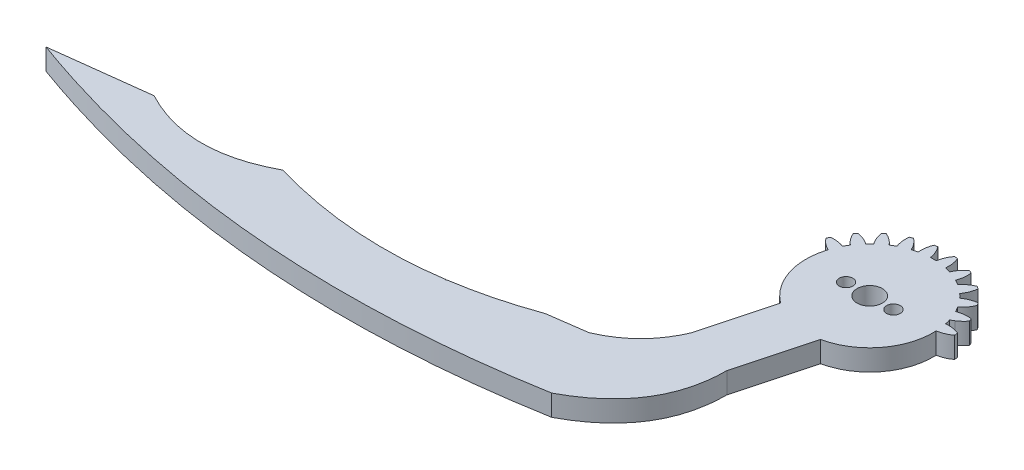
SolidWorks part; units mm, degrees
note: The reader was unsure of these and kept them because the rebuilt part matched: shared geometry of "Sketch6<3>".
ref_plane "Front Plane" through (0, 0, 0) normal (0, 0, 1) x (1, 0, 0)
ref_plane "Top Plane" through (0, 0, 0) normal (0, 1, 0) x (1, 0, 0)
ref_plane "Right Plane" through (0, 0, 0) normal (1, 0, 0) x (0, 0, -1)
sketch "Sketch1" plane through (0, 0, 0) normal (0, 1, 0) x (1, 0, 0)
  line L0 (20.6437, 4) -> (2.0816, 4)
  line L1 (2.0816, -4) -> (20.6437, -4)
  arc A0 (2.0816, 4) -> (3.5217, 5.3071) centre (-0.7683, 8.5867) ccw
  arc A1 (3.5217, 5.3071) -> (3.2829, 5.8838) centre (-10.1063, 0) ccw
  arc A2 (3.2829, 5.8838) -> (0.6271, 5.5703) centre (2.5684, 0.5313) ccw
  arc A3 (0.6271, 5.5703) -> (0.0844, 6.5103) centre (-10.1063, 0) ccw
  arc A4 (0.0844, 6.5103) -> (1.6838, 8.6535) centre (-3.3089, 10.711) ccw
  arc A5 (1.6838, 8.6535) -> (1.3038, 9.1487) centre (-10.1063, 0) ccw
  arc A6 (1.3038, 9.1487) -> (-1.1803, 8.1585) centre (1.999, 3.7936) ccw
  arc A7 (-1.1803, 8.1585) -> (-1.9479, 8.926) centre (-10.1063, 0) ccw
  arc A8 (-1.9479, 8.926) -> (-0.9576, 11.4102) centre (-6.3127, 12.1053) ccw
  arc A9 (-0.9576, 11.4102) -> (-1.4528, 11.7901) centre (-10.1063, 0) ccw
  arc A10 (-1.4528, 11.7901) -> (-3.596, 10.1907) centre (0.6046, 6.7975) ccw
  arc A11 (-3.596, 10.1907) -> (-4.5361, 10.7334) centre (-10.1063, 0) ccw
  arc A12 (-4.5361, 10.7334) -> (-4.2225, 13.3892) centre (-9.5751, 12.6747) ccw
  arc A13 (-4.2225, 13.3892) -> (-4.7992, 13.6281) centre (-10.1063, 0) ccw
  arc A14 (-4.7992, 13.6281) -> (-6.4554, 11.5285) centre (-1.5196, 9.3381) ccw
  arc A15 (-6.4554, 11.5285) -> (-7.5039, 11.8094) centre (-10.1063, 0) ccw
  arc A16 (-7.5039, 11.8094) -> (-7.8884, 14.4558) centre (-12.8736, 12.3803) ccw
  arc A17 (-7.8884, 14.4558) -> (-8.5072, 14.5373) centre (-10.1063, 0) ccw
  arc A18 (-8.5072, 14.5373) -> (-9.5636, 12.0806) centre (-4.2291, 11.2423) ccw
  arc A19 (-9.5636, 12.0806) -> (-10.6491, 12.0806) centre (-10.1063, 0) ccw
  arc A20 (-10.6491, 12.0806) -> (-11.7054, 14.5373) centre (-15.9836, 11.2423) ccw
  arc A21 (-11.7054, 14.5373) -> (-12.3243, 14.4558) centre (-10.1063, 0) ccw
  arc A22 (-12.3243, 14.4558) -> (-12.7088, 11.8094) centre (-7.3391, 12.3803) ccw
  arc A23 (-12.7088, 11.8094) -> (-13.7573, 11.5285) centre (-10.1063, 0) ccw
  arc A24 (-13.7573, 11.5285) -> (-15.4135, 13.6281) centre (-18.6931, 9.3381) ccw
  arc A25 (-15.4135, 13.6281) -> (-15.9901, 13.3892) centre (-10.1063, 0) ccw
  arc A26 (-15.9901, 13.3892) -> (-15.6766, 10.7334) centre (-10.6376, 12.6747) ccw
  arc A27 (-15.6766, 10.7334) -> (-16.6166, 10.1907) centre (-10.1063, 0) ccw
  arc A28 (-16.6166, 10.1907) -> (-18.7599, 11.7901) centre (-20.8173, 6.7975) ccw
  arc A29 (-18.7599, 11.7901) -> (-19.255, 11.4102) centre (-10.1063, 0) ccw
  arc A30 (-19.255, 11.4102) -> (-18.2648, 8.926) centre (-13.9, 12.1053) ccw
  arc A31 (-18.2648, 8.926) -> (-19.0324, 8.1585) centre (-10.1063, 0) ccw
  arc A32 (-19.0324, 8.1585) -> (-21.5165, 9.1487) centre (-22.2117, 3.7936) ccw
  arc A33 (-21.5165, 9.1487) -> (-21.8965, 8.6535) centre (-10.1063, 0) ccw
  arc A34 (-21.8965, 8.6535) -> (-20.2971, 6.5103) centre (-16.9038, 10.711) ccw
  arc A35 (-20.2971, 6.5103) -> (-20.8398, 5.5703) centre (-10.1063, 0) ccw
  arc A36 (-20.8398, 5.5703) -> (-23.4956, 5.8838) centre (-22.7811, 0.5313) ccw
  arc A37 (-23.4956, 5.8838) -> (-23.7344, 5.3071) centre (-10.1063, 0) ccw
  arc A38 (-23.7344, 5.3071) -> (-21.6348, 3.6509) centre (-19.4444, 8.5867) ccw
  arc A39 (-21.6348, 3.6509) -> (-21.9157, 2.6025) centre (-10.1063, 0) ccw
  arc A40 (-21.9157, 2.6025) -> (-24.5622, 2.2179) centre (-22.4867, -2.7673) ccw
  arc A41 (-24.5622, 2.2179) -> (-24.6437, 1.5991) centre (-10.1063, 0) ccw
  arc A42 (-24.6437, 1.5991) -> (-22.1869, 0.5427) centre (-21.3486, 5.8773) ccw
  arc A43 (-22.1869, 0.5427) -> (-22.1869, -0.5427) centre (-10.1063, 0) ccw
  arc A44 (-22.1869, -0.5427) -> (-24.6437, -1.5991) centre (-21.3486, -5.8773) ccw
  arc A45 (-24.6437, -1.5991) -> (-24.5622, -2.2179) centre (-10.1063, 0) ccw
  arc A46 (-24.5622, -2.2179) -> (-21.9157, -2.6025) centre (-22.4867, 2.7673) ccw
  arc A47 (-21.9157, -2.6025) -> (-21.6348, -3.6509) centre (-10.1063, 0) ccw
  arc A48 (-21.6348, -3.6509) -> (-23.7344, -5.3071) centre (-19.4444, -8.5867) ccw
  arc A49 (-23.7344, -5.3071) -> (-23.4956, -5.8838) centre (-10.1063, 0) ccw
  arc A50 (-23.4956, -5.8838) -> (-20.8398, -5.5703) centre (-22.7811, -0.5313) ccw
  arc A51 (-20.8398, -5.5703) -> (-20.2971, -6.5103) centre (-10.1063, 0) ccw
  arc A52 (-20.2971, -6.5103) -> (-21.8965, -8.6535) centre (-16.9038, -10.711) ccw
  arc A53 (-21.8965, -8.6535) -> (-21.5165, -9.1487) centre (-10.1063, 0) ccw
  arc A54 (-21.5165, -9.1487) -> (-19.0324, -8.1585) centre (-22.2117, -3.7936) ccw
  arc A55 (-19.0324, -8.1585) -> (-18.2648, -8.926) centre (-10.1063, 0) ccw
  arc A56 (-18.2648, -8.926) -> (-19.255, -11.4102) centre (-13.9, -12.1053) ccw
  arc A57 (-19.255, -11.4102) -> (-18.7599, -11.7901) centre (-10.1063, 0) ccw
  arc A58 (-18.7599, -11.7901) -> (-16.6166, -10.1907) centre (-20.8173, -6.7975) ccw
  arc A59 (-16.6166, -10.1907) -> (-15.6766, -10.7334) centre (-10.1063, 0) ccw
  arc A60 (-15.6766, -10.7334) -> (-15.9901, -13.3892) centre (-10.6376, -12.6747) ccw
  arc A61 (-15.9901, -13.3892) -> (-15.4135, -13.6281) centre (-10.1063, 0) ccw
  arc A62 (-15.4135, -13.6281) -> (-13.7573, -11.5285) centre (-18.6931, -9.3381) ccw
  arc A63 (-13.7573, -11.5285) -> (-12.7088, -11.8094) centre (-10.1063, 0) ccw
  arc A64 (-12.7088, -11.8094) -> (-12.3243, -14.4558) centre (-7.3391, -12.3803) ccw
  arc A65 (-12.3243, -14.4558) -> (-11.7054, -14.5373) centre (-10.1063, 0) ccw
  arc A66 (-11.7054, -14.5373) -> (-10.6491, -12.0806) centre (-15.9836, -11.2423) ccw
  arc A67 (-10.6491, -12.0806) -> (-9.5636, -12.0806) centre (-10.1063, 0) ccw
  arc A68 (-9.5636, -12.0806) -> (-8.5072, -14.5373) centre (-4.2291, -11.2423) ccw
  arc A69 (-8.5072, -14.5373) -> (-7.8884, -14.4558) centre (-10.1063, 0) ccw
  arc A70 (-7.8884, -14.4558) -> (-7.5039, -11.8094) centre (-12.8736, -12.3803) ccw
  arc A71 (-7.5039, -11.8094) -> (-6.4554, -11.5285) centre (-10.1063, 0) ccw
  arc A72 (-6.4554, -11.5285) -> (-4.7992, -13.6281) centre (-1.5196, -9.3381) ccw
  arc A73 (-4.7992, -13.6281) -> (-4.2225, -13.3892) centre (-10.1063, 0) ccw
  arc A74 (-4.2225, -13.3892) -> (-4.5361, -10.7334) centre (-9.5751, -12.6747) ccw
  arc A75 (-4.5361, -10.7334) -> (-3.596, -10.1907) centre (-10.1063, 0) ccw
  arc A76 (-3.596, -10.1907) -> (-1.4528, -11.7901) centre (0.6046, -6.7975) ccw
  arc A77 (-1.4528, -11.7901) -> (-0.9576, -11.4102) centre (-10.1063, 0) ccw
  arc A78 (-0.9576, -11.4102) -> (-1.9479, -8.926) centre (-6.3127, -12.1053) ccw
  arc A79 (-1.9479, -8.926) -> (-1.1803, -8.1585) centre (-10.1063, 0) ccw
  arc A80 (-1.1803, -8.1585) -> (1.3038, -9.1487) centre (1.999, -3.7936) ccw
  arc A81 (1.3038, -9.1487) -> (1.6838, -8.6535) centre (-10.1063, 0) ccw
  arc A82 (1.6838, -8.6535) -> (0.0844, -6.5103) centre (-3.3089, -10.711) ccw
  arc A83 (0.0844, -6.5103) -> (0.6271, -5.5703) centre (-10.1063, 0) ccw
  arc A84 (0.6271, -5.5703) -> (3.2829, -5.8838) centre (2.5684, -0.5313) ccw
  arc A85 (3.2829, -5.8838) -> (3.5217, -5.3071) centre (-10.1063, 0) ccw
  arc A86 (3.5217, -5.3071) -> (2.0816, -4) centre (-0.7683, -8.5867) ccw
  arc A87 (20.6437, -4) -> (20.6437, 4) centre (20.6437, 0) ccw
  circle A88 centre (-10.1063, 0) radius 1.5
  circle A89 centre (20.6437, 0) radius 1.5
  dimension "D1" = 3
  dimension "D2" = 3
extrude "Boss-Extrude1" add sketch "Sketch1" along normal blind 4
sketch "Sketch3" plane through (0, 4, 0) normal (0, 1, 0) x (1, 0, 0)
  line L0 (-10.1063, 0) -> (-40.8563, 0) construction
  line L1 (-10.1063, 0) -> (-40.5933, -4.0137)
  line L2 (-10.6284, 3.9658) -> (-41.1154, -0.0479)
  line L3 (-9.5842, -3.9658) -> (-40.0712, -7.9795)
  line L4 (-10.1063, 0) -> (-4.5096, 13.5117) construction
  line L5 (-10.1063, 0) -> (-8.1974, 14.4999) construction
  circle A0 centre (-10.1063, 0) radius 1.5
  circle A1 centre (20.6437, 0) radius 1.5 construction
  circle A2 centre (20.6437, 0) radius 1.5
  circle A3 centre (-40.5933, -4.0137) radius 1.75
  circle A4 centre (-40.5933, -4.0137) radius 4
  circle A5 centre (-10.1063, 0) radius 4
  arc A6 (-4.2225, 13.3892) -> (-4.7992, 13.6281) centre (-10.1063, 0) ccw construction
  arc A7 (-7.8884, 14.4558) -> (-8.5072, 14.5373) centre (-10.1063, 0) ccw construction
  dimension "D2" = 3
  dimension "D5" = 3.5
  dimension "D6" = 8
  dimension "D7" = 8
  dimension "D1" = 30.75
  dimension "D4" = 7.5
extrude "Boss-Extrude2" add sketch "Sketch3" against normal blind 4
sketch "Sketch4" plane through (0, 4, 0) normal (0, 1, 0) x (1, 0, 0)
  line L0 (20.6437, 4) -> (2.0816, 4) construction
  line L1 (2.0816, -4) -> (20.6437, -4) construction
  line L2 (20.6437, 4) -> (2.0816, 4)
  line L3 (2.0816, -4) -> (20.6437, -4)
  line L4 (2.0816, 4) -> (1.4381, 3.6001)
  line L5 (-21.6245, -5.5509) -> (-20.8986, -5.4553)
  line L6 (-10.1063, 0) -> (0.0844, 6.5103) construction
  line L7 (-10.1063, 0) -> (1.9742, 0.5427) construction
  line L8 (-24.5755, 2.1296) -> (-41.1154, -0.0479)
  line L9 (-40.0712, -7.9795) -> (-23.5312, -5.8019)
  line L10 (2.0816, -4) -> (20.6437, -4)
  line L11 (20.6437, 4) -> (2.0816, 4)
  line L12 (-21.9429, 2.4762) -> (-41.1154, -0.0479)
  line L13 (-40.0712, -7.9795) -> (-21.6245, -5.5509)
  line L14 (2.0816, -4) -> (20.6437, -4)
  line L15 (20.6437, 4) -> (2.0816, 4)
  circle A0 centre (-10.1063, 0) radius 12.0927
  arc A1 (3.2829, 5.8838) -> (0.6271, 5.5703) centre (2.5684, 0.5313) ccw construction
  arc A2 (3.5217, 5.3071) -> (3.2829, 5.8838) centre (-10.1063, 0) ccw construction
  arc A3 (2.0816, 4) -> (3.5217, 5.3071) centre (-0.7683, 8.5867) ccw construction
  arc A4 (20.6437, -4) -> (20.6437, 4) centre (20.6437, 0) ccw construction
  arc A5 (3.5217, -5.3071) -> (2.0816, -4) centre (-0.7683, -8.5867) ccw construction
  arc A6 (3.2829, -5.8838) -> (3.5217, -5.3071) centre (-10.1063, 0) ccw construction
  arc A7 (0.6271, -5.5703) -> (3.2829, -5.8838) centre (2.5684, -0.5313) ccw construction
  arc A8 (3.2829, 5.8838) -> (0.6271, 5.5703) centre (2.5684, 0.5313) ccw
  arc A9 (3.5217, 5.3071) -> (3.2829, 5.8838) centre (-10.1063, 0) ccw
  arc A10 (2.0816, 4) -> (3.5217, 5.3071) centre (-0.7683, 8.5867) ccw
  arc A11 (20.6437, -4) -> (20.6437, 4) centre (20.6437, 0) ccw
  arc A12 (3.5217, -5.3071) -> (2.0816, -4) centre (-0.7683, -8.5867) ccw
  arc A13 (3.2829, -5.8838) -> (3.5217, -5.3071) centre (-10.1063, 0) ccw
  arc A14 (0.6271, -5.5703) -> (3.2829, -5.8838) centre (2.5684, -0.5313) ccw
  arc A15 (1.9742, 0.5427) -> (4.431, 1.5991) centre (1.1359, 5.8773) ccw
  arc A16 (4.3495, 2.2179) -> (1.7031, 2.6025) centre (2.274, -2.7673) ccw
  arc A17 (4.431, 1.5991) -> (4.3495, 2.2179) centre (-10.1063, 0) ccw
  arc A95 (-21.6348, 3.6509) -> (-21.9157, 2.6025) centre (-10.1063, 0) ccw
  arc A96 (-41.1154, -0.0479) -> (-40.0712, -7.9795) centre (-40.5933, -4.0137) ccw
  arc A97 (-20.2971, -6.5103) -> (-21.8965, -8.6535) centre (-16.9038, -10.711) ccw
  arc A98 (-21.8965, -8.6535) -> (-21.5165, -9.1487) centre (-10.1063, 0) ccw
  arc A99 (-21.5165, -9.1487) -> (-19.0324, -8.1585) centre (-22.2117, -3.7936) ccw
  arc A100 (-19.0324, -8.1585) -> (-18.2648, -8.926) centre (-10.1063, 0) ccw
  arc A101 (-18.2648, -8.926) -> (-19.255, -11.4102) centre (-13.9, -12.1053) ccw
  arc A102 (-19.255, -11.4102) -> (-18.7599, -11.7901) centre (-10.1063, 0) ccw
  arc A103 (-18.7599, -11.7901) -> (-16.6166, -10.1907) centre (-20.8173, -6.7975) ccw
  arc A104 (-16.6166, -10.1907) -> (-15.6766, -10.7334) centre (-10.1063, 0) ccw
  arc A105 (-15.6766, -10.7334) -> (-15.9901, -13.3892) centre (-10.6376, -12.6747) ccw
  arc A106 (-15.9901, -13.3892) -> (-15.4135, -13.6281) centre (-10.1063, 0) ccw
  arc A107 (-15.4135, -13.6281) -> (-13.7573, -11.5285) centre (-18.6931, -9.3381) ccw
  arc A108 (-13.7573, -11.5285) -> (-12.7088, -11.8094) centre (-10.1063, 0) ccw
  arc A109 (-12.7088, -11.8094) -> (-12.3243, -14.4558) centre (-7.3391, -12.3803) ccw
  arc A110 (-12.3243, -14.4558) -> (-11.7054, -14.5373) centre (-10.1063, 0) ccw
  arc A111 (-11.7054, -14.5373) -> (-10.6491, -12.0806) centre (-15.9836, -11.2423) ccw
  arc A112 (-10.6491, -12.0806) -> (-9.5636, -12.0806) centre (-10.1063, 0) ccw
  arc A113 (-9.5636, -12.0806) -> (-8.5072, -14.5373) centre (-4.2291, -11.2423) ccw
  arc A114 (-8.5072, -14.5373) -> (-7.8884, -14.4558) centre (-10.1063, 0) ccw
  arc A115 (-7.8884, -14.4558) -> (-7.5039, -11.8094) centre (-12.8736, -12.3803) ccw
  arc A116 (-7.5039, -11.8094) -> (-6.4554, -11.5285) centre (-10.1063, 0) ccw
  arc A117 (-6.4554, -11.5285) -> (-4.7992, -13.6281) centre (-1.5196, -9.3381) ccw
  arc A118 (-4.7992, -13.6281) -> (-4.2225, -13.3892) centre (-10.1063, 0) ccw
  arc A119 (-4.2225, -13.3892) -> (-4.5361, -10.7334) centre (-9.5751, -12.6747) ccw
  arc A120 (-4.5361, -10.7334) -> (-3.596, -10.1907) centre (-10.1063, 0) ccw
  arc A121 (-3.596, -10.1907) -> (-1.4528, -11.7901) centre (0.6046, -6.7975) ccw
  arc A122 (-1.4528, -11.7901) -> (-0.9576, -11.4102) centre (-10.1063, 0) ccw
  arc A123 (-0.9576, -11.4102) -> (-1.9479, -8.926) centre (-6.3127, -12.1053) ccw
  arc A124 (-1.9479, -8.926) -> (-1.1803, -8.1585) centre (-10.1063, 0) ccw
  arc A125 (-1.1803, -8.1585) -> (1.3038, -9.1487) centre (1.999, -3.7936) ccw
  arc A126 (1.3038, -9.1487) -> (1.6838, -8.6535) centre (-10.1063, 0) ccw
  arc A127 (1.6838, -8.6535) -> (0.0844, -6.5103) centre (-3.3089, -10.711) ccw
  arc A128 (0.0844, -6.5103) -> (0.6271, -5.5703) centre (-10.1063, 0) ccw
  arc A129 (0.6271, -5.5703) -> (3.2829, -5.8838) centre (2.5684, -0.5313) ccw
  arc A130 (3.2829, -5.8838) -> (3.5217, -5.3071) centre (-10.1063, 0) ccw
  arc A131 (3.5217, -5.3071) -> (2.0816, -4) centre (-0.7683, -8.5867) ccw
  arc A132 (20.6437, -4) -> (20.6437, 4) centre (20.6437, 0) ccw
  arc A133 (2.0816, 4) -> (3.5217, 5.3071) centre (-0.7683, 8.5867) ccw
  arc A134 (3.5217, 5.3071) -> (3.2829, 5.8838) centre (-10.1063, 0) ccw
  arc A135 (3.2829, 5.8838) -> (0.6271, 5.5703) centre (2.5684, 0.5313) ccw
  arc A136 (0.6271, 5.5703) -> (0.0844, 6.5103) centre (-10.1063, 0) ccw
  arc A137 (0.0844, 6.5103) -> (1.6838, 8.6535) centre (-3.3089, 10.711) ccw
  arc A138 (1.6838, 8.6535) -> (1.3038, 9.1487) centre (-10.1063, 0) ccw
  arc A139 (1.3038, 9.1487) -> (-1.1803, 8.1585) centre (1.999, 3.7936) ccw
  arc A140 (-1.1803, 8.1585) -> (-1.9479, 8.926) centre (-10.1063, 0) ccw
  arc A141 (-1.9479, 8.926) -> (-0.9576, 11.4102) centre (-6.3127, 12.1053) ccw
  arc A142 (-0.9576, 11.4102) -> (-1.4528, 11.7901) centre (-10.1063, 0) ccw
  arc A143 (-1.4528, 11.7901) -> (-3.596, 10.1907) centre (0.6046, 6.7975) ccw
  arc A144 (-3.596, 10.1907) -> (-4.5361, 10.7334) centre (-10.1063, 0) ccw
  arc A145 (-4.5361, 10.7334) -> (-4.2225, 13.3892) centre (-9.5751, 12.6747) ccw
  arc A146 (-4.2225, 13.3892) -> (-4.7992, 13.6281) centre (-10.1063, 0) ccw
  arc A147 (-4.7992, 13.6281) -> (-6.4554, 11.5285) centre (-1.5196, 9.3381) ccw
  arc A148 (-6.4554, 11.5285) -> (-7.5039, 11.8094) centre (-10.1063, 0) ccw
  arc A149 (-7.5039, 11.8094) -> (-7.8884, 14.4558) centre (-12.8736, 12.3803) ccw
  arc A150 (-7.8884, 14.4558) -> (-8.5072, 14.5373) centre (-10.1063, 0) ccw
  arc A151 (-8.5072, 14.5373) -> (-9.5636, 12.0806) centre (-4.2291, 11.2423) ccw
  arc A152 (-9.5636, 12.0806) -> (-10.6491, 12.0806) centre (-10.1063, 0) ccw
  arc A153 (-10.6491, 12.0806) -> (-11.7054, 14.5373) centre (-15.9836, 11.2423) ccw
  arc A154 (-11.7054, 14.5373) -> (-12.3243, 14.4558) centre (-10.1063, 0) ccw
  arc A155 (-12.3243, 14.4558) -> (-12.7088, 11.8094) centre (-7.3391, 12.3803) ccw
  arc A156 (-12.7088, 11.8094) -> (-13.7573, 11.5285) centre (-10.1063, 0) ccw
  arc A157 (-13.7573, 11.5285) -> (-15.4135, 13.6281) centre (-18.6931, 9.3381) ccw
  arc A158 (-15.4135, 13.6281) -> (-15.9901, 13.3892) centre (-10.1063, 0) ccw
  arc A159 (-15.9901, 13.3892) -> (-15.6766, 10.7334) centre (-10.6376, 12.6747) ccw
  arc A160 (-15.6766, 10.7334) -> (-16.6166, 10.1907) centre (-10.1063, 0) ccw
  arc A161 (-16.6166, 10.1907) -> (-18.7599, 11.7901) centre (-20.8173, 6.7975) ccw
  arc A162 (-18.7599, 11.7901) -> (-19.255, 11.4102) centre (-10.1063, 0) ccw
  arc A163 (-19.255, 11.4102) -> (-18.2648, 8.926) centre (-13.9, 12.1053) ccw
  arc A164 (-18.2648, 8.926) -> (-19.0324, 8.1585) centre (-10.1063, 0) ccw
  arc A165 (-19.0324, 8.1585) -> (-21.5165, 9.1487) centre (-22.2117, 3.7936) ccw
  arc A166 (-21.5165, 9.1487) -> (-21.8965, 8.6535) centre (-10.1063, 0) ccw
  arc A167 (-21.8965, 8.6535) -> (-20.2971, 6.5103) centre (-16.9038, 10.711) ccw
  arc A168 (-20.2971, 6.5103) -> (-20.8398, 5.5703) centre (-10.1063, 0) ccw
  arc A169 (-20.8398, 5.5703) -> (-23.4956, 5.8838) centre (-22.7811, 0.5313) ccw
  arc A170 (-23.4956, 5.8838) -> (-23.7344, 5.3071) centre (-10.1063, 0) ccw
  arc A171 (-23.7344, 5.3071) -> (-21.6348, 3.6509) centre (-19.4444, 8.5867) ccw
  arc A172 (-21.6348, 3.6509) -> (-21.9157, 2.6025) centre (-10.1063, 0) ccw
  arc A175 (-23.4956, -5.8838) -> (-20.8398, -5.5703) centre (-22.7811, -0.5313) ccw
  arc A176 (-41.1154, -0.0479) -> (-40.0712, -7.9795) centre (-40.5933, -4.0137) ccw
  arc A177 (-20.2971, -6.5103) -> (-21.8965, -8.6535) centre (-16.9038, -10.711) ccw
  arc A178 (-21.8965, -8.6535) -> (-21.5165, -9.1487) centre (-10.1063, 0) ccw
  arc A179 (-21.5165, -9.1487) -> (-19.0324, -8.1585) centre (-22.2117, -3.7936) ccw
  arc A180 (-19.0324, -8.1585) -> (-18.2648, -8.926) centre (-10.1063, 0) ccw
  arc A181 (-18.2648, -8.926) -> (-19.255, -11.4102) centre (-13.9, -12.1053) ccw
  arc A182 (-19.255, -11.4102) -> (-18.7599, -11.7901) centre (-10.1063, 0) ccw
  arc A183 (-18.7599, -11.7901) -> (-16.6166, -10.1907) centre (-20.8173, -6.7975) ccw
  arc A184 (-16.6166, -10.1907) -> (-15.6766, -10.7334) centre (-10.1063, 0) ccw
  arc A185 (-15.6766, -10.7334) -> (-15.9901, -13.3892) centre (-10.6376, -12.6747) ccw
  arc A186 (-15.9901, -13.3892) -> (-15.4135, -13.6281) centre (-10.1063, 0) ccw
  arc A187 (-15.4135, -13.6281) -> (-13.7573, -11.5285) centre (-18.6931, -9.3381) ccw
  arc A188 (-13.7573, -11.5285) -> (-12.7088, -11.8094) centre (-10.1063, 0) ccw
  arc A189 (-12.7088, -11.8094) -> (-12.3243, -14.4558) centre (-7.3391, -12.3803) ccw
  arc A190 (-12.3243, -14.4558) -> (-11.7054, -14.5373) centre (-10.1063, 0) ccw
  arc A191 (-11.7054, -14.5373) -> (-10.6491, -12.0806) centre (-15.9836, -11.2423) ccw
  arc A192 (-10.6491, -12.0806) -> (-9.5636, -12.0806) centre (-10.1063, 0) ccw
  arc A193 (-9.5636, -12.0806) -> (-8.5072, -14.5373) centre (-4.2291, -11.2423) ccw
  arc A194 (-8.5072, -14.5373) -> (-7.8884, -14.4558) centre (-10.1063, 0) ccw
  arc A195 (-7.8884, -14.4558) -> (-7.5039, -11.8094) centre (-12.8736, -12.3803) ccw
  arc A196 (-7.5039, -11.8094) -> (-6.4554, -11.5285) centre (-10.1063, 0) ccw
  arc A197 (-6.4554, -11.5285) -> (-4.7992, -13.6281) centre (-1.5196, -9.3381) ccw
  arc A198 (-4.7992, -13.6281) -> (-4.2225, -13.3892) centre (-10.1063, 0) ccw
  arc A199 (-4.2225, -13.3892) -> (-4.5361, -10.7334) centre (-9.5751, -12.6747) ccw
  arc A200 (-4.5361, -10.7334) -> (-3.596, -10.1907) centre (-10.1063, 0) ccw
  arc A201 (-3.596, -10.1907) -> (-1.4528, -11.7901) centre (0.6046, -6.7975) ccw
  arc A202 (-1.4528, -11.7901) -> (-0.9576, -11.4102) centre (-10.1063, 0) ccw
  arc A203 (-0.9576, -11.4102) -> (-1.9479, -8.926) centre (-6.3127, -12.1053) ccw
  arc A204 (-1.9479, -8.926) -> (-1.1803, -8.1585) centre (-10.1063, 0) ccw
  arc A205 (-1.1803, -8.1585) -> (1.3038, -9.1487) centre (1.999, -3.7936) ccw
  arc A206 (1.3038, -9.1487) -> (1.6838, -8.6535) centre (-10.1063, 0) ccw
  arc A207 (1.6838, -8.6535) -> (0.0844, -6.5103) centre (-3.3089, -10.711) ccw
  arc A208 (0.0844, -6.5103) -> (0.6271, -5.5703) centre (-10.1063, 0) ccw
  arc A209 (0.6271, -5.5703) -> (3.2829, -5.8838) centre (2.5684, -0.5313) ccw
  arc A210 (3.2829, -5.8838) -> (3.5217, -5.3071) centre (-10.1063, 0) ccw
  arc A211 (3.5217, -5.3071) -> (2.0816, -4) centre (-0.7683, -8.5867) ccw
  arc A212 (20.6437, -4) -> (20.6437, 4) centre (20.6437, 0) ccw
  arc A213 (2.0816, 4) -> (3.5217, 5.3071) centre (-0.7683, 8.5867) ccw
  arc A214 (3.5217, 5.3071) -> (3.2829, 5.8838) centre (-10.1063, 0) ccw
  arc A215 (3.2829, 5.8838) -> (0.6271, 5.5703) centre (2.5684, 0.5313) ccw
  arc A216 (0.6271, 5.5703) -> (0.0844, 6.5103) centre (-10.1063, 0) ccw
  arc A217 (0.0844, 6.5103) -> (1.6838, 8.6535) centre (-3.3089, 10.711) ccw
  arc A218 (1.6838, 8.6535) -> (1.3038, 9.1487) centre (-10.1063, 0) ccw
  arc A219 (1.3038, 9.1487) -> (-1.1803, 8.1585) centre (1.999, 3.7936) ccw
  arc A220 (-1.1803, 8.1585) -> (-1.9479, 8.926) centre (-10.1063, 0) ccw
  arc A221 (-1.9479, 8.926) -> (-0.9576, 11.4102) centre (-6.3127, 12.1053) ccw
  arc A222 (-0.9576, 11.4102) -> (-1.4528, 11.7901) centre (-10.1063, 0) ccw
  arc A223 (-1.4528, 11.7901) -> (-3.596, 10.1907) centre (0.6046, 6.7975) ccw
  arc A224 (-3.596, 10.1907) -> (-4.5361, 10.7334) centre (-10.1063, 0) ccw
  arc A225 (-4.5361, 10.7334) -> (-4.2225, 13.3892) centre (-9.5751, 12.6747) ccw
  arc A226 (-4.2225, 13.3892) -> (-4.7992, 13.6281) centre (-10.1063, 0) ccw
  arc A227 (-4.7992, 13.6281) -> (-6.4554, 11.5285) centre (-1.5196, 9.3381) ccw
  arc A228 (-6.4554, 11.5285) -> (-7.5039, 11.8094) centre (-10.1063, 0) ccw
  arc A229 (-7.5039, 11.8094) -> (-7.8884, 14.4558) centre (-12.8736, 12.3803) ccw
  arc A230 (-7.8884, 14.4558) -> (-8.5072, 14.5373) centre (-10.1063, 0) ccw
  arc A231 (-8.5072, 14.5373) -> (-9.5636, 12.0806) centre (-4.2291, 11.2423) ccw
  arc A232 (-9.5636, 12.0806) -> (-10.6491, 12.0806) centre (-10.1063, 0) ccw
  arc A233 (-10.6491, 12.0806) -> (-11.7054, 14.5373) centre (-15.9836, 11.2423) ccw
  arc A234 (-11.7054, 14.5373) -> (-12.3243, 14.4558) centre (-10.1063, 0) ccw
  arc A235 (-12.3243, 14.4558) -> (-12.7088, 11.8094) centre (-7.3391, 12.3803) ccw
  arc A236 (-12.7088, 11.8094) -> (-13.7573, 11.5285) centre (-10.1063, 0) ccw
  arc A237 (-13.7573, 11.5285) -> (-15.4135, 13.6281) centre (-18.6931, 9.3381) ccw
  arc A238 (-15.4135, 13.6281) -> (-15.9901, 13.3892) centre (-10.1063, 0) ccw
  arc A239 (-15.9901, 13.3892) -> (-15.6766, 10.7334) centre (-10.6376, 12.6747) ccw
  arc A240 (-15.6766, 10.7334) -> (-16.6166, 10.1907) centre (-10.1063, 0) ccw
  arc A241 (-16.6166, 10.1907) -> (-18.7599, 11.7901) centre (-20.8173, 6.7975) ccw
  arc A242 (-18.7599, 11.7901) -> (-19.255, 11.4102) centre (-10.1063, 0) ccw
  arc A243 (-19.255, 11.4102) -> (-18.2648, 8.926) centre (-13.9, 12.1053) ccw
  arc A244 (-18.2648, 8.926) -> (-19.0324, 8.1585) centre (-10.1063, 0) ccw
  arc A245 (-19.0324, 8.1585) -> (-21.5165, 9.1487) centre (-22.2117, 3.7936) ccw
  arc A246 (-21.5165, 9.1487) -> (-21.8965, 8.6535) centre (-10.1063, 0) ccw
  arc A247 (-21.8965, 8.6535) -> (-20.2971, 6.5103) centre (-16.9038, 10.711) ccw
  arc A248 (-20.2971, 6.5103) -> (-20.8398, 5.5703) centre (-10.1063, 0) ccw
  arc A249 (-20.8398, 5.5703) -> (-23.4956, 5.8838) centre (-22.7811, 0.5313) ccw
  arc A250 (-23.4956, 5.8838) -> (-23.7344, 5.3071) centre (-10.1063, 0) ccw
  arc A251 (-23.7344, 5.3071) -> (-21.6348, 3.6509) centre (-19.4444, 8.5867) ccw
  arc A252 (-23.4956, -5.8838) -> (-20.8398, -5.5703) centre (-22.7811, -0.5313) ccw
  arc A253 (-20.8398, -5.5703) -> (-20.2971, -6.5103) centre (-10.1063, 0) ccw
  arc A254 (-20.8398, -5.5703) -> (-20.2971, -6.5103) centre (-10.1063, 0) ccw
  arc A255 (-23.5312, -5.8019) -> (-23.4956, -5.8838) centre (-10.1063, 0) ccw
  arc A256 (-23.5312, -5.8019) -> (-23.4956, -5.8838) centre (-10.1063, 0) ccw
  arc A257 (-21.9157, 2.6025) -> (-24.5622, 2.2179) centre (-22.4867, -2.7673) ccw
  arc A258 (-21.9157, 2.6025) -> (-24.5622, 2.2179) centre (-22.4867, -2.7673) ccw
  arc A259 (-24.5622, 2.2179) -> (-24.5755, 2.1296) centre (-10.1063, 0) ccw
  arc A260 (-24.5622, 2.2179) -> (-24.5755, 2.1296) centre (-10.1063, 0) ccw
  point P40 (-10.1063, 0)
  dimension "D2" = 24.1855
  dimension "D4" = 30
  dimension "D1" = 0
  dimension "D3" = 2
extrude "Cut-Extrude1" cut sketch "Sketch4" against normal blind 4 contours A178 A179 A0 L5 A177 | A182 A183 A0 A181 | A186 A187 A0 A185 | A190 A191 A0 A189 | A194 A195 A0 A193 | A198 A199 A0 A197 | A202 A203 A0 A201 | A206 A207 A0 A205 | A258 A260 L12 A0 | L13 A256 A252 A0 L5 | A0 A14 A13 A12 L3 A11 L2 L4
sketch "Sketch5" plane through (0, 4, 0) normal (0, 1, 0) x (1, 0, 0)
  circle A0 centre (-10.1063, 0) radius 2.4
  circle A1 centre (-5.6063, 0) radius 1.3
  circle A2 centre (-14.6063, 0) radius 1.3
  circle A3 centre (-10.1063, 0) radius 1.5 construction
  dimension "D1" = 4.8
  dimension "D2" = 2.6
  dimension "D3" = 2.6
  dimension "D4" = 4.5
  dimension "D5" = 9
extrude "Cut-Extrude2" cut sketch "Sketch5" against normal up to next contours A2 | A1 | A0
sketch "Sketch6" plane through (0, 4, 0) normal (0, 1, 0) x (1, 0, 0)
  line L0 (-10.1063, 0) -> (27.4558, 0) construction
  line L6 (-10.1063, 0) -> (-10.1063, 50.6275) construction
  line L7 (-49.9947, -31.0378) -> (-31.4327, -31.0378)
  line L9 (-31.4327, -31.0378) -> (-30.7345, -31.267)
  line L10 (-110.9546, -35.0378) -> (-129.2447, -37.2757)
  line L11 (-16.653, -6.8971) -> (-20.9868, -23.0712)
  line L12 (-6.9937, -9.4853) -> (-11.3793, -25.8525)
  line L15 (1.4381, 3.6001) -> (2.0816, 4)
  line L16 (-7.7003, -31.4377) -> (-7.0568, -31.0378)
  line L17 (-30.7064, -32.7034) -> (-49.8584, -35.379)
  line L18 (-21.9429, 2.4762) -> (-41.1154, -0.0479)
  line L19 (-40.0712, -7.9795) -> (-20.8986, -5.4553)
  line L20 (1.4381, 3.6001) -> (2.0816, 4)
  line L21 (-23.6599, -5.715) -> (-42.8324, -8.2391)
  line L22 (-41.7882, -16.1707) -> (-22.6156, -13.6466)
  line L23 (-21.9429, 2.4762) -> (-41.1154, -0.0479) construction
  line L24 (-21.9429, 2.4762) -> (-41.1154, -0.0479)
  line L25 (-20.8986, -5.4553) -> (-40.0712, -7.9795) construction
  line L26 (-20.8986, -5.4553) -> (-40.0712, -7.9795)
  arc A46 (-20.9868, -23.0712) -> (-31.1213, -32.7614) centre (-19.2447, -35.0378) ccw
  arc A92 (-4.7074, -33.4387) -> (3.539, -25.9102) centre (-0.5842, -29.6745) cw
  arc A93 (-4.7889, -32.8199) -> (-4.7074, -33.4387) centre (-19.2447, -35.0378) cw
  arc A94 (-7.4353, -32.4354) -> (-4.7889, -32.8199) centre (-6.8644, -37.8051) cw
  arc A95 (-7.7163, -31.3869) -> (-7.4353, -32.4354) centre (-19.2447, -35.0378) cw
  arc A96 (-5.6166, -29.7307) -> (-7.7163, -31.3869) centre (-9.9067, -26.4511) cw
  arc A97 (-5.8555, -29.154) -> (-5.6166, -29.7307) centre (-19.2447, -35.0378) cw
  arc A98 (-8.5113, -29.4676) -> (-5.8555, -29.154) centre (-6.57, -34.5065) cw
  arc A99 (-9.054, -28.5275) -> (-8.5113, -29.4676) centre (-19.2447, -35.0378) cw
  arc A100 (-7.4546, -26.3843) -> (-9.054, -28.5275) centre (-12.4473, -24.3268) cw
  arc A101 (-7.8346, -25.8891) -> (-7.4546, -26.3843) centre (-19.2447, -35.0378) cw
  arc A102 (-10.3187, -26.8793) -> (-7.8346, -25.8891) centre (-7.1394, -31.2442) cw
  arc A103 (-11.0863, -26.1118) -> (-10.3187, -26.8793) centre (-19.2447, -35.0378) cw
  arc A104 (-10.096, -23.6277) -> (-11.0863, -26.1118) centre (-15.4511, -22.9325) cw
  arc A105 (-10.5912, -23.2477) -> (-10.096, -23.6277) centre (-19.2447, -35.0378) cw
  arc A106 (-10.6929, -23.2908) -> (-10.5912, -23.2477) centre (-8.5337, -28.2404) cw
  arc A115 (-20.8438, -20.5005) -> (-20.4536, -21.0814) centre (-25.122, -23.7956) cw
  arc A116 (-21.4627, -20.582) -> (-20.8438, -20.5005) centre (-19.2447, -35.0378) cw
  arc A117 (-21.8472, -23.2284) -> (-21.4627, -20.582) centre (-16.4775, -22.6575) cw
  arc A118 (-22.8956, -23.5094) -> (-21.8472, -23.2284) centre (-19.2447, -35.0378) cw
  arc A119 (-24.5519, -21.4097) -> (-22.8956, -23.5094) centre (-27.8314, -25.6998) cw
  arc A120 (-25.1285, -21.6486) -> (-24.5519, -21.4097) centre (-19.2447, -35.0378) cw
  arc A121 (-24.815, -24.3044) -> (-25.1285, -21.6486) centre (-19.776, -22.3631) cw
  arc A122 (-25.755, -24.8471) -> (-24.815, -24.3044) centre (-19.2447, -35.0378) cw
  arc A123 (-27.8983, -23.2477) -> (-25.755, -24.8471) centre (-29.9557, -28.2404) cw
  arc A124 (-28.3934, -23.6277) -> (-27.8983, -23.2477) centre (-19.2447, -35.0378) cw
  arc A125 (-27.4032, -26.1118) -> (-28.3934, -23.6277) centre (-23.0384, -22.9325) cw
  arc A126 (-28.1707, -26.8793) -> (-27.4032, -26.1118) centre (-19.2447, -35.0378) cw
  arc A127 (-30.6549, -25.8891) -> (-28.1707, -26.8793) centre (-31.3501, -31.2442) cw
  arc A128 (-31.0349, -26.3843) -> (-30.6549, -25.8891) centre (-19.2447, -35.0378) cw
  arc A129 (-29.4355, -28.5275) -> (-31.0349, -26.3843) centre (-26.0422, -24.3268) cw
  arc A130 (-29.9782, -29.4676) -> (-29.4355, -28.5275) centre (-19.2447, -35.0378) cw
  arc A131 (-32.634, -29.154) -> (-29.9782, -29.4676) centre (-31.9195, -34.5065) cw
  arc A132 (-32.8728, -29.7307) -> (-32.634, -29.154) centre (-19.2447, -35.0378) cw
  arc A133 (-31.4327, -31.0378) -> (-32.8728, -29.7307) centre (-28.5828, -26.4511) cw
  arc A134 (-52.9621, -37.7202) -> (-49.9947, -31.0378) centre (-49.9947, -35.0378) cw
  arc A135 (3.539, -25.9102) -> (-24.3078, -46.1789) centre (-16.9719, -26.9941) cw
  arc A136 (-8.1265, -11.9296) -> (-17.7857, -9.3414) centre (-10.1063, 0) ccw
  arc A137 (-24.0523, -46.1339) -> (-11.3793, -25.8525) centre (-19.2447, -35.0378) ccw
  arc A138 (-24.0523, -46.1339) -> (-11.3793, -25.8525) centre (-19.2447, -35.0378) ccw
  arc A139 (-20.9868, -23.0712) -> (-31.1213, -32.7614) centre (-19.2447, -35.0378) ccw
  arc A186 (2.0816, 4) -> (3.5217, 5.3071) centre (-0.7683, 8.5867) ccw
  arc A187 (3.5217, 5.3071) -> (3.2829, 5.8838) centre (-10.1063, 0) ccw
  arc A188 (3.2829, 5.8838) -> (0.6271, 5.5703) centre (2.5684, 0.5313) ccw
  arc A189 (0.6271, 5.5703) -> (0.0844, 6.5103) centre (-10.1063, 0) ccw
  arc A190 (0.0844, 6.5103) -> (1.6838, 8.6535) centre (-3.3089, 10.711) ccw
  arc A191 (1.6838, 8.6535) -> (1.3038, 9.1487) centre (-10.1063, 0) ccw
  arc A192 (1.3038, 9.1487) -> (-1.1803, 8.1585) centre (1.999, 3.7936) ccw
  arc A193 (-1.1803, 8.1585) -> (-1.9479, 8.926) centre (-10.1063, 0) ccw
  arc A194 (-1.9479, 8.926) -> (-0.9576, 11.4102) centre (-6.3127, 12.1053) ccw
  arc A195 (-0.9576, 11.4102) -> (-1.4528, 11.7901) centre (-10.1063, 0) ccw
  arc A196 (-1.4528, 11.7901) -> (-3.596, 10.1907) centre (0.6046, 6.7975) ccw
  arc A197 (-3.596, 10.1907) -> (-4.5361, 10.7334) centre (-10.1063, 0) ccw
  arc A198 (-4.5361, 10.7334) -> (-4.2225, 13.3892) centre (-9.5751, 12.6747) ccw
  arc A199 (-4.2225, 13.3892) -> (-4.7992, 13.6281) centre (-10.1063, 0) ccw
  arc A200 (-4.7992, 13.6281) -> (-6.4554, 11.5285) centre (-1.5196, 9.3381) ccw
  arc A201 (-6.4554, 11.5285) -> (-7.5039, 11.8094) centre (-10.1063, 0) ccw
  arc A202 (-7.5039, 11.8094) -> (-7.8884, 14.4558) centre (-12.8736, 12.3803) ccw
  arc A203 (-7.8884, 14.4558) -> (-8.5072, 14.5373) centre (-10.1063, 0) ccw
  arc A204 (-8.5072, 14.5373) -> (-9.5636, 12.0806) centre (-4.2291, 11.2423) ccw
  arc A205 (-9.5636, 12.0806) -> (-10.6491, 12.0806) centre (-10.1063, 0) ccw
  arc A206 (-10.6491, 12.0806) -> (-11.7054, 14.5373) centre (-15.9836, 11.2423) ccw
  arc A207 (-11.7054, 14.5373) -> (-12.3243, 14.4558) centre (-10.1063, 0) ccw
  arc A208 (-12.3243, 14.4558) -> (-12.7088, 11.8094) centre (-7.3391, 12.3803) ccw
  arc A209 (-12.7088, 11.8094) -> (-13.7573, 11.5285) centre (-10.1063, 0) ccw
  arc A210 (-13.7573, 11.5285) -> (-15.4135, 13.6281) centre (-18.6931, 9.3381) ccw
  arc A211 (-15.4135, 13.6281) -> (-15.9901, 13.3892) centre (-10.1063, 0) ccw
  arc A212 (-15.9901, 13.3892) -> (-15.6766, 10.7334) centre (-10.6376, 12.6747) ccw
  arc A213 (-15.6766, 10.7334) -> (-16.6166, 10.1907) centre (-10.1063, 0) ccw
  arc A214 (-16.6166, 10.1907) -> (-18.7599, 11.7901) centre (-20.8173, 6.7975) ccw
  arc A215 (-18.7599, 11.7901) -> (-19.255, 11.4102) centre (-10.1063, 0) ccw
  arc A216 (-19.255, 11.4102) -> (-18.2648, 8.926) centre (-13.9, 12.1053) ccw
  arc A217 (-18.2648, 8.926) -> (-19.0324, 8.1585) centre (-10.1063, 0) ccw
  arc A218 (-19.0324, 8.1585) -> (-21.5165, 9.1487) centre (-22.2117, 3.7936) ccw
  arc A219 (-21.5165, 9.1487) -> (-21.8965, 8.6535) centre (-10.1063, 0) ccw
  arc A220 (-21.8965, 8.6535) -> (-20.2971, 6.5103) centre (-16.9038, 10.711) ccw
  arc A221 (-20.2971, 6.5103) -> (-20.8398, 5.5703) centre (-10.1063, 0) ccw
  arc A222 (-20.8398, 5.5703) -> (-23.4956, 5.8838) centre (-22.7811, 0.5313) ccw
  arc A223 (-23.4956, 5.8838) -> (-23.7344, 5.3071) centre (-10.1063, 0) ccw
  arc A224 (-23.7344, 5.3071) -> (-21.6348, 3.6509) centre (-19.4444, 8.5867) ccw
  arc A225 (-21.6348, 3.6509) -> (-21.9429, 2.4762) centre (-10.1063, 0) ccw
  arc A226 (-41.1154, -0.0479) -> (-40.0712, -7.9795) centre (-40.5933, -4.0137) ccw
  arc A227 (-20.8986, -5.4553) -> (1.9742, 0.5427) centre (-10.1063, 0) ccw
  arc A228 (-7.0568, -31.0378) -> (-5.6166, -29.7307) centre (-9.9067, -26.4511) ccw
  arc A229 (-5.6166, -29.7307) -> (-5.8555, -29.154) centre (-19.2447, -35.0378) ccw
  arc A230 (-5.8555, -29.154) -> (-8.5113, -29.4676) centre (-6.57, -34.5065) ccw
  arc A231 (-8.5113, -29.4676) -> (-9.054, -28.5275) centre (-19.2447, -35.0378) ccw
  arc A232 (-9.054, -28.5275) -> (-7.4546, -26.3843) centre (-12.4473, -24.3268) ccw
  arc A233 (-7.4546, -26.3843) -> (-7.8346, -25.8891) centre (-19.2447, -35.0378) ccw
  arc A234 (-7.8346, -25.8891) -> (-10.3187, -26.8793) centre (-7.1394, -31.2442) ccw
  arc A235 (-10.3187, -26.8793) -> (-11.0863, -26.1118) centre (-19.2447, -35.0378) ccw
  arc A236 (-11.0863, -26.1118) -> (-10.096, -23.6277) centre (-15.4511, -22.9325) ccw
  arc A237 (-10.096, -23.6277) -> (-10.5912, -23.2477) centre (-19.2447, -35.0378) ccw
  arc A238 (-10.5912, -23.2477) -> (-10.6929, -23.2908) centre (-8.5337, -28.2404) ccw
  arc A239 (1.9742, 0.5427) -> (4.431, 1.5991) centre (1.1359, 5.8773) ccw
  arc A240 (4.431, 1.5991) -> (4.3495, 2.2179) centre (-10.1063, 0) ccw
  arc A241 (4.3495, 2.2179) -> (1.7031, 2.6025) centre (2.274, -2.7673) ccw
  arc A242 (1.7031, 2.6025) -> (1.4381, 3.6001) centre (-10.1063, 0) ccw
  arc A243 (2.0816, 4) -> (3.5217, 5.3071) centre (-0.7683, 8.5867) ccw
  arc A244 (3.5217, 5.3071) -> (3.2829, 5.8838) centre (-10.1063, 0) ccw
  arc A245 (3.2829, 5.8838) -> (0.6271, 5.5703) centre (2.5684, 0.5313) ccw
  arc A246 (0.6271, 5.5703) -> (0.0844, 6.5103) centre (-10.1063, 0) ccw
  arc A247 (0.0844, 6.5103) -> (1.6838, 8.6535) centre (-3.3089, 10.711) ccw
  arc A248 (-20.4536, -21.0814) -> (-20.8438, -20.5005) centre (-25.122, -23.7956) ccw
  arc A249 (-20.8438, -20.5005) -> (-21.4627, -20.582) centre (-19.2447, -35.0378) ccw
  arc A250 (-21.4627, -20.582) -> (-21.8472, -23.2284) centre (-16.4775, -22.6575) ccw
  arc A251 (-21.8472, -23.2284) -> (-22.8956, -23.5094) centre (-19.2447, -35.0378) ccw
  arc A252 (-22.8956, -23.5094) -> (-24.5519, -21.4097) centre (-27.8314, -25.6998) ccw
  arc A253 (-24.5519, -21.4097) -> (-25.1285, -21.6486) centre (-19.2447, -35.0378) ccw
  arc A254 (-25.1285, -21.6486) -> (-24.815, -24.3044) centre (-19.776, -22.3631) ccw
  arc A255 (-24.815, -24.3044) -> (-25.755, -24.8471) centre (-19.2447, -35.0378) ccw
  arc A256 (-25.755, -24.8471) -> (-27.8983, -23.2477) centre (-29.9557, -28.2404) ccw
  arc A257 (-27.8983, -23.2477) -> (-28.3934, -23.6277) centre (-19.2447, -35.0378) ccw
  arc A258 (-28.3934, -23.6277) -> (-27.4032, -26.1118) centre (-23.0384, -22.9325) ccw
  arc A259 (-27.4032, -26.1118) -> (-28.1707, -26.8793) centre (-19.2447, -35.0378) ccw
  arc A260 (-28.1707, -26.8793) -> (-30.6549, -25.8891) centre (-31.3501, -31.2442) ccw
  arc A261 (-30.6549, -25.8891) -> (-31.0349, -26.3843) centre (-19.2447, -35.0378) ccw
  arc A262 (-31.0349, -26.3843) -> (-29.4355, -28.5275) centre (-26.0422, -24.3268) ccw
  arc A263 (-29.4355, -28.5275) -> (-29.9782, -29.4676) centre (-19.2447, -35.0378) ccw
  arc A264 (-29.9782, -29.4676) -> (-32.634, -29.154) centre (-31.9195, -34.5065) ccw
  arc A265 (-32.634, -29.154) -> (-32.8728, -29.7307) centre (-19.2447, -35.0378) ccw
  arc A266 (-32.8728, -29.7307) -> (-30.7732, -31.3869) centre (-28.5828, -26.4511) ccw
  arc A267 (-30.7732, -31.3869) -> (-30.7064, -32.7034) centre (-18.6805, -31.4331) ccw
  arc A268 (-49.8584, -35.379) -> (-52.9621, -37.7202) centre (-49.3049, -39.3405) ccw
  arc A269 (-20.5159, -47.0636) -> (3.539, -25.9102) centre (-8.4884, -36.4869) ccw
  arc A270 (3.539, -25.9102) -> (-4.7074, -33.4387) centre (-0.5842, -29.6745) ccw
  arc A271 (-4.7074, -33.4387) -> (-4.7889, -32.8199) centre (-19.2447, -35.0378) ccw
  arc A272 (-4.7889, -32.8199) -> (-7.4353, -32.4354) centre (-6.8644, -37.8051) ccw
  arc A273 (-7.4353, -32.4354) -> (-7.7003, -31.4377) centre (-19.2447, -35.0378) ccw
  arc A274 (1.6838, 8.6535) -> (1.3038, 9.1487) centre (-10.1063, 0) ccw
  arc A275 (1.3038, 9.1487) -> (-1.1803, 8.1585) centre (1.999, 3.7936) ccw
  arc A276 (-1.1803, 8.1585) -> (-1.9479, 8.926) centre (-10.1063, 0) ccw
  arc A277 (-1.9479, 8.926) -> (-0.9576, 11.4102) centre (-6.3127, 12.1053) ccw
  arc A278 (-0.9576, 11.4102) -> (-1.4528, 11.7901) centre (-10.1063, 0) ccw
  arc A279 (-1.4528, 11.7901) -> (-3.596, 10.1907) centre (0.6046, 6.7975) ccw
  arc A280 (-3.596, 10.1907) -> (-4.5361, 10.7334) centre (-10.1063, 0) ccw
  arc A281 (-4.5361, 10.7334) -> (-4.2225, 13.3892) centre (-9.5751, 12.6747) ccw
  arc A282 (-4.2225, 13.3892) -> (-4.7992, 13.6281) centre (-10.1063, 0) ccw
  arc A283 (-4.7992, 13.6281) -> (-6.4554, 11.5285) centre (-1.5196, 9.3381) ccw
  arc A284 (-6.4554, 11.5285) -> (-7.5039, 11.8094) centre (-10.1063, 0) ccw
  arc A285 (-7.5039, 11.8094) -> (-7.8884, 14.4558) centre (-12.8736, 12.3803) ccw
  arc A286 (-7.8884, 14.4558) -> (-8.5072, 14.5373) centre (-10.1063, 0) ccw
  arc A287 (-8.5072, 14.5373) -> (-9.5636, 12.0806) centre (-4.2291, 11.2423) ccw
  arc A288 (-9.5636, 12.0806) -> (-10.6491, 12.0806) centre (-10.1063, 0) ccw
  arc A289 (-10.6491, 12.0806) -> (-11.7054, 14.5373) centre (-15.9836, 11.2423) ccw
  arc A290 (-11.7054, 14.5373) -> (-12.3243, 14.4558) centre (-10.1063, 0) ccw
  arc A291 (-12.3243, 14.4558) -> (-12.7088, 11.8094) centre (-7.3391, 12.3803) ccw
  arc A292 (-12.7088, 11.8094) -> (-13.7573, 11.5285) centre (-10.1063, 0) ccw
  arc A293 (-13.7573, 11.5285) -> (-15.4135, 13.6281) centre (-18.6931, 9.3381) ccw
  arc A294 (-15.4135, 13.6281) -> (-15.9901, 13.3892) centre (-10.1063, 0) ccw
  arc A295 (-15.9901, 13.3892) -> (-15.6766, 10.7334) centre (-10.6376, 12.6747) ccw
  arc A296 (-15.6766, 10.7334) -> (-16.6166, 10.1907) centre (-10.1063, 0) ccw
  arc A297 (-16.6166, 10.1907) -> (-18.7599, 11.7901) centre (-20.8173, 6.7975) ccw
  arc A298 (-18.7599, 11.7901) -> (-19.255, 11.4102) centre (-10.1063, 0) ccw
  arc A299 (-19.255, 11.4102) -> (-18.2648, 8.926) centre (-13.9, 12.1053) ccw
  arc A300 (-18.2648, 8.926) -> (-19.0324, 8.1585) centre (-10.1063, 0) ccw
  arc A301 (-19.0324, 8.1585) -> (-21.5165, 9.1487) centre (-22.2117, 3.7936) ccw
  arc A302 (-21.5165, 9.1487) -> (-21.8965, 8.6535) centre (-10.1063, 0) ccw
  arc A303 (-21.8965, 8.6535) -> (-20.2971, 6.5103) centre (-16.9038, 10.711) ccw
  arc A304 (-20.2971, 6.5103) -> (-20.8398, 5.5703) centre (-10.1063, 0) ccw
  arc A305 (-20.8398, 5.5703) -> (-23.4956, 5.8838) centre (-22.7811, 0.5313) ccw
  arc A306 (-23.4956, 5.8838) -> (-23.7344, 5.3071) centre (-10.1063, 0) ccw
  arc A307 (-23.7344, 5.3071) -> (-21.6348, 3.6509) centre (-19.4444, 8.5867) ccw
  arc A308 (-21.6348, 3.6509) -> (-21.9429, 2.4762) centre (-10.1063, 0) ccw
  arc A309 (-42.8324, -8.2391) -> (-41.7882, -16.1707) centre (-42.3103, -12.2049) ccw
  arc A310 (-20.8986, -5.4553) -> (1.9742, 0.5427) centre (-10.1063, 0) ccw
  arc A311 (1.9742, 0.5427) -> (4.431, 1.5991) centre (1.1359, 5.8773) ccw
  arc A312 (4.431, 1.5991) -> (4.3495, 2.2179) centre (-10.1063, 0) ccw
  arc A313 (4.3495, 2.2179) -> (1.7031, 2.6025) centre (2.274, -2.7673) ccw
  arc A314 (1.7031, 2.6025) -> (1.4381, 3.6001) centre (-10.1063, 0) ccw
  arc A315 (-41.1154, -0.0479) -> (-40.0712, -7.9795) centre (-40.5933, -4.0137) ccw construction
  circle A316 centre (-40.5933, -4.0137) radius 1.75
  circle A317 centre (-40.5933, -4.0137) radius 1.75
  arc A318 (-41.1154, -0.0479) -> (-40.0712, -7.9795) centre (-40.5933, -4.0137) ccw
  spline S0 degree 2 poles (-30.7064, -32.7034) (-23.8892, -29.8109) (-20.9868, -23.0712) knots 0 0 0 1 1 1
  spline S1 degree 2 poles (-24.3078, -46.1789) (-11.3259, -39.2979) (-11.3793, -25.8525) knots 0 0 0 1 1 1
  spline S3 degree 2 poles (-24.0523, -46.1339) (-78.4311, -55.7367) (-129.2447, -37.2757) knots 0 0 0 1 1 1
  spline S4 degree 2 poles (-86.4738, -35.0378) (-98.6793, -41.5996) (-110.9546, -35.0378) knots 0 0 0 1 1 1
  spline S5 degree 2 poles (-31.4327, -31.0378) (-58.3731, -43.3272) (-86.4738, -35.0378) knots 0 0 0 1 1 1
  dimension "D1" = 0
  dimension "D2" = 27.8535
  dimension "D3" = 0
extrude "Boss-Extrude3" add sketch "Sketch6" against normal up to surface (4 mm away) contours L17 S5 A268 A134 S4 L10 S3 S1 L12 A310 L11 S0 up to face at (-14.6063, 0, 1.3)
extrude "Cut-Extrude3" cut sketch "Sketch6<3>" against normal blind 10 contours S5 L17 A268 | L21 A309 L22 A136
sketch "Sketch6<3>" plane through (0, 4, 0) normal (0, 1, 0) x (1, 0, 0) same geometry as "Sketch6"
